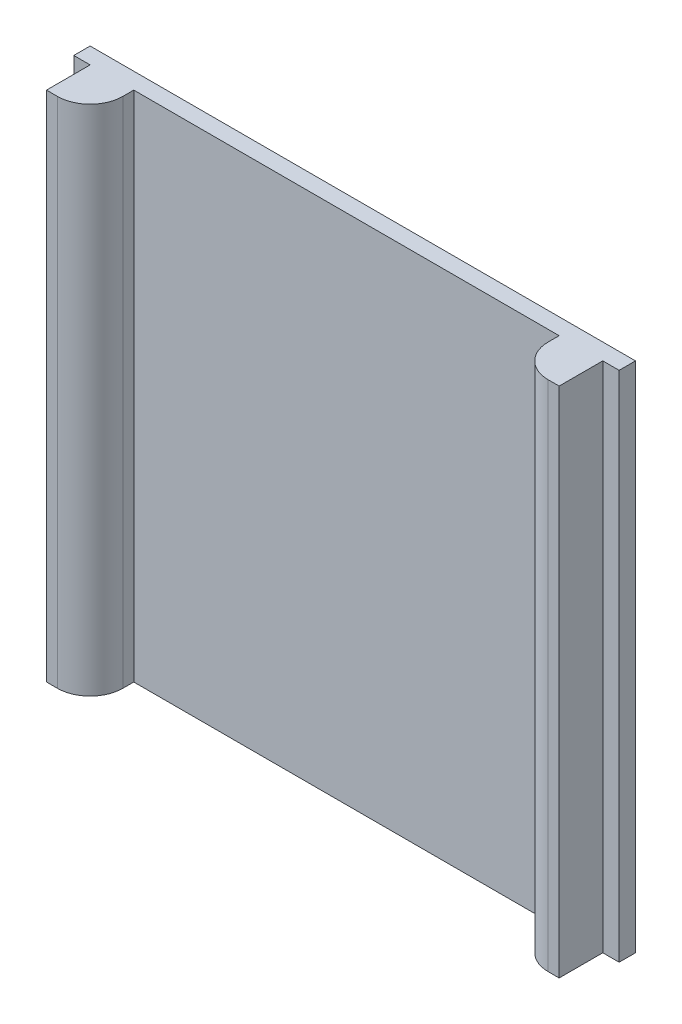
SolidWorks part; units mm, degrees
material "3.0205 (EN-AW 1200)"
ref_plane "Piano frontale" through (0, 0, 0) normal (0, 0, 1) x (1, 0, 0)
ref_plane "Piano superiore" through (0, 0, 0) normal (0, 1, 0) x (1, 0, 0)
ref_plane "Piano destro" through (0, 0, 0) normal (1, 0, 0) x (0, 0, -1)
sketch "Schizzo1" plane through (0, 0, 0) normal (0, 0, 1) x (1, 0, 0)
  line L1 (-250, -235) -> (250, -235)
  line L2 (-250, -235) -> (-250, 235)
  line L3 (-250, 235) -> (250, 235)
  line L4 (250, -235) -> (250, 235)
  line L5 (-250, -235) -> (250, 235) construction
  line L6 (-250, 235) -> (250, -235) construction
  point P0 (0, 0)
  dimension "D1" = 500
  dimension "D2" = 470
extrude "Estrusione-Estrusione1" add sketch "Schizzo1" along normal blind 15
sketch "Schizzo2" plane through (0, 0, 15) normal (0, 0, 1) x (1, 0, 0)
  line L0 (250, 235) -> (-250, 235) construction
  line L1 (-235, 235) -> (-195, 235)
  line L2 (-235, 235) -> (-235, -235)
  line L3 (-235, -235) -> (-195, -235)
  line L4 (-195, 235) -> (-195, -235)
  line L5 (-250, -235) -> (250, -235) construction
  line L6 (-250, 235) -> (-250, -235) construction
  dimension "D1" = 40
  dimension "D2" = 15
extrude "Estrusione-Estrusione2" add sketch "Schizzo2" along normal blind 40
fillet "Raccordo1" radius 30 1 edges at (-195, 0, 55)
mirror "Specchia1" about plane through (0, 0, 0) normal (1, 0, 0) of "Raccordo1", "Estrusione-Estrusione2"
